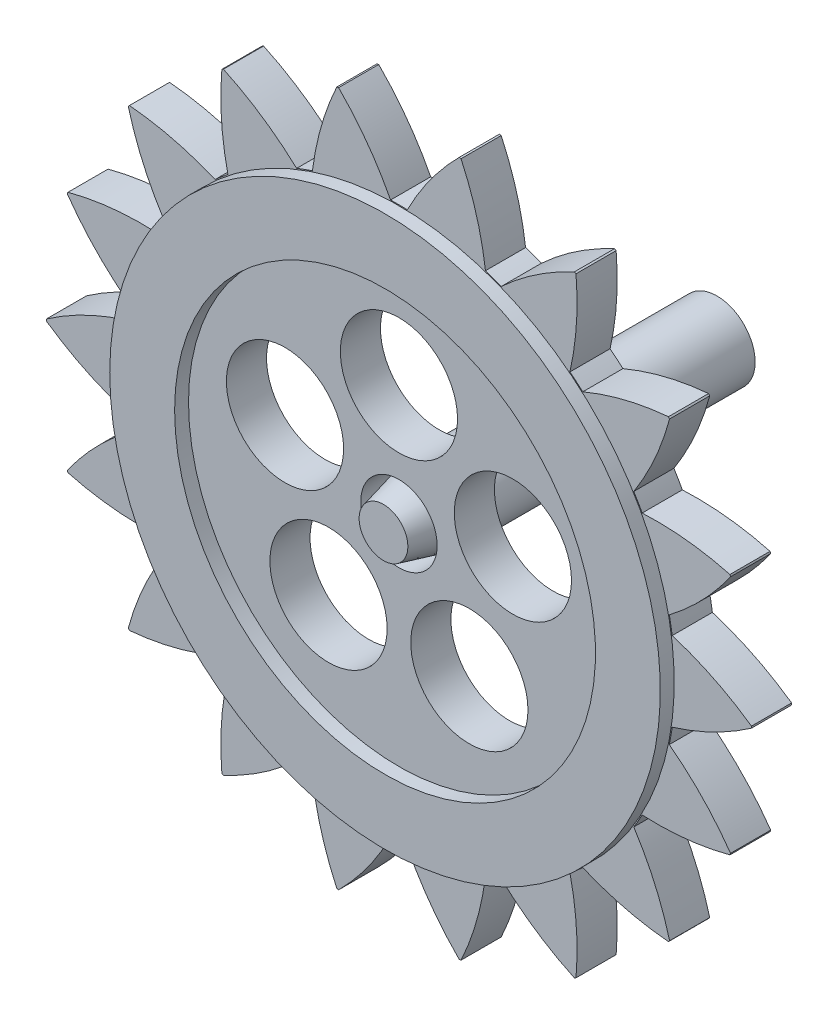
SolidWorks part; units mm, degrees
note: The reader was unsure of these and kept them because the rebuilt part matched: shared geometry of "Esquisse1<2>".
ref_plane "Plan de face" through (0, 0, 0) normal (0, 0, 1) x (1, 0, 0)
ref_plane "Plan de dessus" through (0, 0, 0) normal (0, 1, 0) x (1, 0, 0)
ref_plane "Plan de droite" through (0, 0, 0) normal (1, 0, 0) x (0, 0, -1)
sketch "Esquisse1" plane through (0, 0, 0) normal (0, 0, 1) x (1, 0, 0)
  circle A1 centre (0, 0) radius 0.2476
  circle A2 centre (0, 0) radius 2.2841
extrude "Boss.-Extru.1" add sketch "Esquisse1" along normal blind 0.26
extrude "Boss.-Extru.2" add sketch "Esquisse1<2>" along normal blind 0.36 draft 14 and the other way blind 1.8 separate body contours A1
sketch "Esquisse1<2>" plane through (0, 0, 0) normal (0, 0, 1) x (1, 0, 0) same geometry as "Esquisse1"
sketch "Esquisse5" plane through (0, 0, 0.26) normal (0, 0, 1) x (1, 0, 0)
  line L0 (0, 0) -> (0, 2.4509) construction
  arc A0 (0.5459, 2.3894) -> (-0.5459, 2.3894) centre (0, 0) ccw
  arc A1 (0.0543, 1.7882) -> (-0.0543, 1.7882) centre (0, 0) ccw
  arc A2 (0.5459, 2.3894) -> (0.0543, 1.7882) centre (1.7051, 0.94) ccw
  arc A3 (-0.5459, 2.3894) -> (-0.0543, 1.7882) centre (-1.7051, 0.94) cw
extrude "Enlèv. mat.-Extru.2" cut sketch "Esquisse5" against normal blind 0.3
pattern_circular "Répétition circulaire2" count 18 over 360 about axis through (0, 0, 0) along (0, 0, 1) of "Enlèv. mat.-Extru.2"
sketch "Esquisse6" plane through (0, 0, 0.26) normal (0, 0, 1) x (1, 0, 0)
  circle A0 centre (0, 0) radius 1.7835
  circle A1 centre (0, 0) radius 1.3632
extrude "Boss.-Extru.4" add sketch "Esquisse6" along normal blind 0.09
sketch "Esquisse7" plane through (0, 0, 0.26) normal (0, 0, 1) x (1, 0, 0)
  circle A0 centre (0, 0.7762) radius 0.3797
  circle A1 centre (0.7382, 0.2399) radius 0.3797
  circle A2 centre (0.4562, -0.6279) radius 0.3797
  circle A3 centre (-0.4562, -0.6279) radius 0.3797
  circle A4 centre (-0.7382, 0.2399) radius 0.3797
extrude "Enlèv. mat.-Extru.3" cut sketch "Esquisse7" against normal blind 0.29
